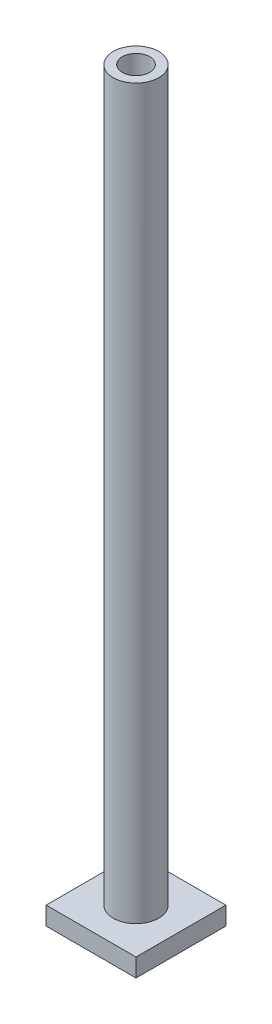
SolidWorks part; units mm, degrees
ref_plane "Front Plane" through (0, 0, 0) normal (0, 0, 1) x (1, 0, 0)
ref_plane "Top Plane" through (0, 0, 0) normal (0, 1, 0) x (1, 0, 0)
ref_plane "Right Plane" through (0, 0, 0) normal (1, 0, 0) x (0, 0, -1)
sketch "Sketch1" plane through (0, 0, 0) normal (0, 1, 0) x (1, 0, 0)
  line L1 (7.9, 7.9) -> (-7.9, 7.9)
  line L2 (7.9, 7.9) -> (7.9, -7.9)
  line L3 (7.9, -7.9) -> (-7.9, -7.9)
  line L4 (-7.9, 7.9) -> (-7.9, -7.9)
  line L5 (7.9, 7.9) -> (-7.9, -7.9) construction
  line L6 (7.9, -7.9) -> (-7.9, 7.9) construction
  point P0 (0, 0)
  dimension "D1" = 15.8
extrude "Base" add sketch "Sketch1" along normal blind 3.2
sketch "Sketch2" plane through (0, 0, 0) normal (0, -1, 0) x (1, 0, 0)
  line L0 (0, 6.5) -> (0, -6.5) construction
  line L1 (6.5, 6.5) -> (-6.5, 6.5)
  line L2 (6.5, 6.5) -> (6.5, -6.5)
  line L3 (6.5, -6.5) -> (-6.5, -6.5)
  line L4 (-6.5, 6.5) -> (-6.5, -6.5)
  line L5 (6.5, 6.5) -> (-6.5, -6.5) construction
  line L6 (6.5, -6.5) -> (-6.5, 6.5) construction
  line L7 (-6.5, 0) -> (6.5, 0) construction
  line L8 (-7.9, -7.9) -> (-7.9, 7.9) construction
  line L9 (0, -6.5) -> (0, -7.9) construction
  line L10 (7.9, -7.9) -> (-7.9, -7.9) construction
  line L12 (-1.25, -6.5) -> (1.25, -6.5)
  line L13 (-1.25, -6.5) -> (-1.25, -7.9)
  line L14 (-1.25, -7.9) -> (1.25, -7.9)
  line L15 (1.25, -6.5) -> (1.25, -7.9)
  line L16 (-1.25, -6.5) -> (1.25, -7.9) construction
  line L17 (-1.25, -7.9) -> (1.25, -6.5) construction
  line L18 (-1.25, -2.1651) -> (1.25, -2.1651)
  line L19 (-1.25, -2.1651) -> (-1.25, -6.5)
  line L20 (-1.25, -6.5) -> (1.25, -6.5)
  line L21 (1.25, -2.1651) -> (1.25, -6.5)
  circle A4 centre (0, 0) radius 3.5
  circle A5 centre (0, 0) radius 2.5
  point P0 (0, 0)
  point P6 (0, -7.2)
  line M4 (-7.9, -7.9) -> (7.9, -7.9)
  dimension "D4" = 5
  dimension "D2" = 1.4
  dimension "D5" = 1
  dimension "D1" = 2.5
extrude "Bottom cut" cut sketch "Sketch2" against normal offset from surface (2 mm away) 1.2 contours A4 L21 L3 L2 L1 L4 L19 | L18 A5 | L18 A5 | A5 L19 A4 L21 | A4 L19 L3 L21 | L15 L3 L13 M4 region at (6.3162, 0, 0) region at (0, 0, -7.2) region at (0, 0, -4.9613) region at (0, 0, -2.9054) region at (0, 0, -2.2998) region at (0, 0, 0.0683) up to face at (0, 3.2, 0)
sketch "Sketch3" plane through (0, 3.2, 0) normal (0, 1, 0) x (1, 0, 0)
  circle A0 centre (0, 0) radius 4
  circle A1 centre (0, 0) radius 2.4
  dimension "D1" = 8
  dimension "D2" = 1.6
extrude "Lamp post" add sketch "Sketch3" along normal blind 128
sketch "Sketch4" plane through (0, 3.2, 0) normal (0, 1, 0) x (1, 0, 0)
  circle A0 centre (0, 0) radius 2.4 construction
  circle A1 centre (0, 0) radius 2.4
extrude "Wire bottom cut" cut sketch "Sketch4" against normal up to next
equation "\"P\"= \"LegoUnit\" * 5"
equation "\"D1@Sketch1\" = \"BrickSize\" * 2 - \"Padding\""
equation "\"Padding\"= \"LegoUnit\" / 8"
equation "\"SmallHeight\"= \"LegoUnit\" * 2"
equation "\"LargeHight\"= \"LegoUnit\" * 6"
equation "\"D1@Base\" = \"SmallHeight\""
equation "\"InsetDiameter\"= \"LegoUnit\" * 2 - \"Padding\" * 3"
equation "\"LegoUnit\"=1.6"
equation "\"BrickSize\"= \"LegoUnit\" * 5"
equation "\"WallSize\" = \"LegoUnit\" - \"Padding\""
equation "\"D2@Sketch2\"=\"WallSize\""
equation "\"BumpSize\"= \"LegoUnit\" * 3"
equation "\"InsideBumpSize\"= \"BumpSize\" + \"Padding\""
equation "\"InnerWallSize\"= \"Padding\" * 5"
equation "\"D5@Sketch2\"=\"InnerWallSize\""
equation "\"CeilingSize\"= \"LegoUnit\" - \"Padding\" * 2"
equation "\"D1@Bottom cut\" = \"CeilingSize\""
equation "\"D4@Sketch2\"=\"InsideBumpSize\""
equation "\"D1@Sketch3\"=\"BrickSize\""
equation "\"D2@Sketch3\"=\"LegoUnit\""
equation "\"D1@Lamp post\"=\"SmallHeight\" * 40"
